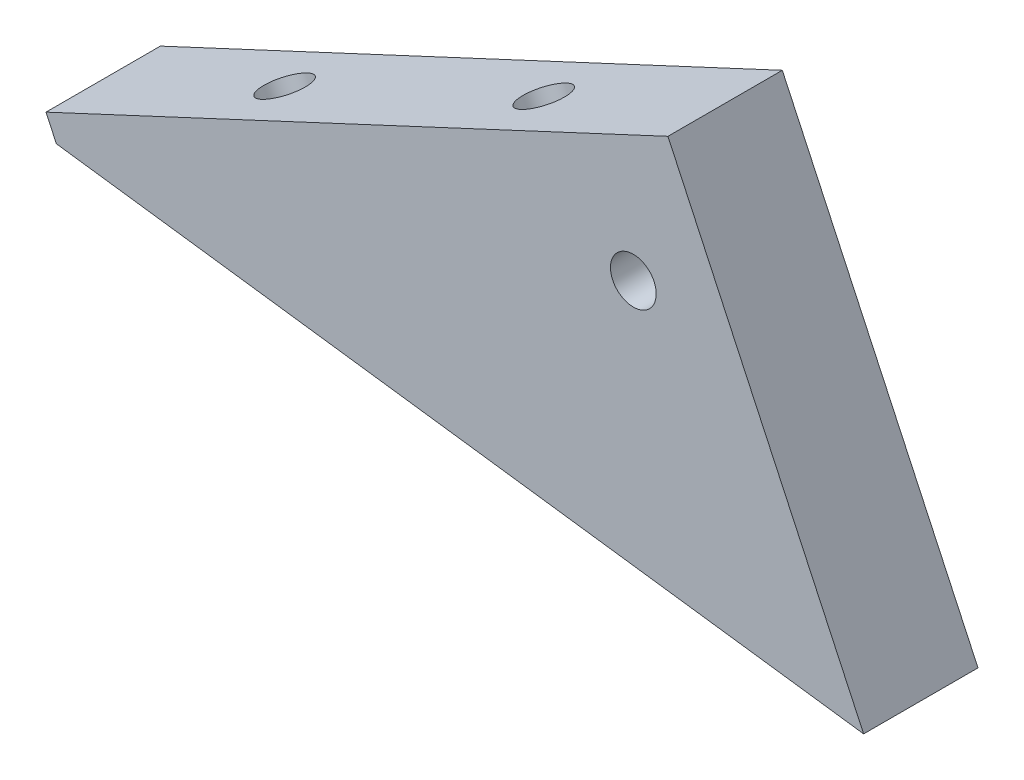
SolidWorks part; units mm, degrees
material "ABS"
ref_plane "Front Plane" through (0, 0, 0) normal (0, 0, 1) x (1, 0, 0)
ref_plane "Top Plane" through (0, 0, 0) normal (0, 1, 0) x (1, 0, 0)
ref_plane "Right Plane" through (0, 0, 0) normal (1, 0, 0) x (0, 0, -1)
sketch "Sketch1" plane through (0, 0, 0) normal (0, 0, 1) x (1, 0, 0)
  line L0 (125.2807, -8.1077) -> (108.169, 28.5884)
  line L1 (-85.1981, -61.5801) -> (277.3251, 107.4672) construction
  line L2 (108.169, 28.5884) -> (53.7905, 3.2313)
  line L3 (53.7905, 3.2313) -> (54.6972, 1.287)
  line L4 (54.6972, 1.287) -> (125.2807, -8.1077)
  line L7 (50.7481, 1.8126) -> (339.9495, -36.6803) construction
  dimension "D1" = 60
extrude "Boss-Extrude1" add sketch "Sketch1" against normal blind 10
sketch "Sketch2" plane through (8.3697, -17.9488, 0) normal (-0.4226, 0.9063, 0) x (0.9063, 0.4226, 0)
  line L0 (50.1164, 5) -> (110.1164, 5) construction
  line L1 (50.1164, 10) -> (50.1164, 0) construction
  line L2 (110.1164, 10) -> (110.1164, 0) construction
  line L3 (80.1164, 10) -> (80.1164, 0) construction
  line L4 (92.6164, 0.9585) -> (96.1164, 2.9793)
  line L5 (96.1164, 2.9793) -> (96.1164, 7.0207)
  line L6 (96.1164, 7.0207) -> (92.6164, 9.0415)
  line L7 (92.6164, 9.0415) -> (89.1164, 7.0207)
  line L8 (89.1164, 7.0207) -> (89.1164, 2.9793)
  line L9 (89.1164, 2.9793) -> (92.6164, 0.9585)
  line L10 (110.1164, 10) -> (50.1164, 10) construction
  line L11 (110.1164, 0) -> (50.1164, 0) construction
  line L12 (71.1164, 2.9793) -> (67.6164, 0.9585)
  line L13 (67.6164, 0.9585) -> (64.1164, 2.9793)
  line L14 (71.1164, 7.0207) -> (71.1164, 2.9793)
  line L15 (67.6164, 9.0415) -> (71.1164, 7.0207)
  line L16 (64.1164, 7.0207) -> (67.6164, 9.0415)
  line L17 (64.1164, 2.9793) -> (64.1164, 7.0207)
  circle A0 centre (92.6164, 5) radius 3.5 construction
  circle A1 centre (92.6164, 5) radius 2
  circle A2 centre (67.6164, 5) radius 3.5 construction
  circle A3 centre (67.6164, 5) radius 2
  dimension "D3" = 4
  dimension "D1" = 17.5
  dimension "D2" = 7
extrude "Cut-Extrude1" cut sketch "Sketch2" against normal through all contours A3 | A1 region at (92.3086, 21.1926, -5) region at (69.6509, 10.6271, -5)
extrude "Cut-Extrude2" cut sketch "Sketch2<3>" against normal through all from offset 4 offset against normal yes
sketch "Sketch2<3>" plane through (8.3697, -17.9488, 0) normal (-0.4226, 0.9063, 0) x (0.9063, 0.4226, 0) same geometry as "Sketch2"
sketch "Sketch3" plane through (1.1205, 8.4181, 0) normal (-0.1319, -0.9913, 0) x (0.9913, -0.1319, 0)
  line L0 (125.2552, -5) -> (54.0492, -5) construction
  line L1 (125.2552, -10) -> (125.2552, 0) construction
  line L2 (54.0492, -10) -> (54.0492, 0) construction
  circle A0 centre (87.7143, -5) radius 2
  circle A1 centre (113.3156, -5) radius 2
  circle A2 centre (113.3156, -5) radius 1.5 construction
  circle A3 centre (87.7143, -5) radius 1.5 construction
  dimension "D1" = 4
  dimension "D2" = 4
extrude "Cut-Extrude3" cut sketch "Sketch3" against normal blind 10
sketch "Sketch4" plane through (0, 0, 0) normal (0, 0, 1) x (1, 0, 0)
  line L0 (125.2807, -8.1077) -> (108.169, 28.5884) construction
  line L1 (109.1708, 15.7922) -> (107.4628, 19.455)
  line L2 (107.4628, 19.455) -> (103.4367, 19.8072)
  line L3 (103.4367, 19.8072) -> (101.1187, 16.4966)
  line L4 (101.1187, 16.4966) -> (102.8266, 12.8338)
  line L5 (102.8266, 12.8338) -> (106.8527, 12.4816)
  line L6 (106.8527, 12.4816) -> (109.1708, 15.7922)
  line L7 (108.169, 28.5884) -> (53.7905, 3.2313) construction
  circle A0 centre (105.1447, 16.1444) radius 2
  circle A1 centre (105.1447, 16.1444) radius 3.5 construction
  dimension "D4" = 4
  dimension "D1" = 8
  dimension "D2" = 10
  dimension "D3" = 7
  dimension "D5" = 0
extrude "Cut-Extrude4" cut sketch "Sketch4" against normal blind 10 contours A0 region at (105.1447, 16.1444, 0)
extrude "Cut-Extrude5" cut sketch "Sketch4<3>" along normal blind 5 from surface starting at face at (107.1447, 16.1444, -10)
sketch "Sketch4<3>" plane through (0, 0, 0) normal (0, 0, 1) x (1, 0, 0) same geometry as "Sketch4"
